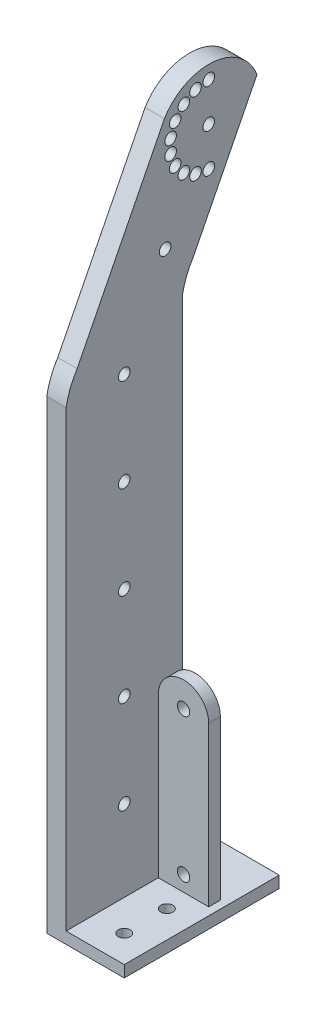
SolidWorks part; units mm, degrees
ref_plane "前视基准面" through (0, 0, 0) normal (0, 0, 1) x (1, 0, 0)
ref_plane "上视基准面" through (0, 0, 0) normal (0, 1, 0) x (1, 0, 0)
ref_plane "右视基准面" through (0, 0, 0) normal (1, 0, 0) x (0, 0, -1)
sketch "草图1" plane through (0, 0, 0) normal (1, 0, 0) x (0, 0, -1)
  line L0 (-15, 0) -> (15, 0)
  line L1 (-15, 0) -> (-15, 120)
  line L2 (15, 0) -> (15, 130)
  line L3 (17.8333, 137.2485) -> (34.2776, 169.8061)
  line L4 (-12.1667, 127.2485) -> (10.3753, 171.8787)
  line L5 (13.1525, 169.9179) -> (21.8127, 164.9179) construction
  line L7 (11.218, 143.9417) -> (10.5417, 142.6028) construction
  line L8 (21.8127, 164.9179) -> (15.3848, 172.5784) construction
  line L9 (21.8127, 164.9179) -> (11.9646, 166.6544) construction
  line L10 (11.9646, 163.1814) -> (21.8127, 164.9179) construction
  line L11 (21.8127, 164.9179) -> (18.3925, 155.521) construction
  line L12 (21.8127, 164.9179) -> (21.8127, 154.9179) construction
  line L13 (18.3925, 174.3148) -> (21.8127, 164.9179) construction
  line L14 (21.8127, 164.9179) -> (13.1525, 159.9179) construction
  line L15 (21.8127, 164.9179) -> (21.8127, 174.9179) construction
  line L16 (15.3848, 157.2575) -> (21.8127, 164.9179) construction
  arc A0 (15, 130) -> (17.8333, 137.2485) centre (34.6882, 126.4823) cw
  arc A1 (-12.1667, 127.2485) -> (-15, 120) centre (4.6882, 116.4823) ccw
  circle A2 centre (0, 23.9341) radius 1.5
  circle A3 centre (0, 47.9341) radius 1.5
  circle A4 centre (0, 71.9341) radius 1.5
  circle A5 centre (0, 95.9341) radius 1.5
  circle A7 centre (21.8127, 164.9179) radius 10 construction
  circle A8 centre (10.5417, 142.6028) radius 1.5
  circle A9 centre (0, 119.9341) radius 1.5
  arc A10 (34.2776, 169.8061) -> (10.3753, 171.8787) centre (21.8127, 164.9179) ccw
  circle A11 centre (21.8127, 164.9179) radius 1.5
  circle A13 centre (11.9646, 166.6544) radius 1.5
  circle A14 centre (11.9646, 163.1814) radius 1.5
  circle A15 centre (13.1525, 159.9179) radius 1.5
  circle A16 centre (15.3848, 157.2575) radius 1.5
  circle A19 centre (21.8127, 154.9179) radius 1.5
  circle A20 centre (18.3925, 155.521) radius 1.5
  circle A21 centre (13.1525, 169.9179) radius 1.5
  circle A22 centre (15.3848, 172.5784) radius 1.5
  circle A23 centre (18.3925, 174.3148) radius 1.5
  circle A24 centre (21.8127, 174.9179) radius 1.5
  point P3 (0, 0)
  dimension "D5" = 20
  dimension "D7" = 20
  dimension "D4" = 3
  dimension "D9" = 3
  dimension "D11" = 3
  dimension "D16" = 20
  dimension "D20" = 20
  dimension "D22" = 20
  dimension "D24" = 20
  dimension "D1" = 30
  dimension "D2" = 120
  dimension "D3" = 130
  dimension "D6" = 24
  dimension "D8" = 25
  dimension "D12" = 25
  dimension "D10" = 15
  dimension "D13" = 24
  dimension "D14" = 24
  dimension "D15" = 24
  dimension "D17" = 20
  dimension "D18" = 20
  dimension "D19" = 20
  dimension "D21" = 20
  dimension "D23" = 20
extrude "凸台-拉伸2" add sketch "草图1" against normal blind 5
ref_plane "基准面1" through (-5, 0, 0) normal (-1, 0, 0) x (0, 0, 1)
sketch "草图3" plane through (-5, 0, 0) normal (-1, 0, 0) x (0, 0, 1)
  line L25 (-10, 5) -> (10, 5)
  line L26 (-10, 130.4183) -> (-10, 5)
  line L27 (10, 5) -> (10, 119.5247)
  line L28 (-28.6572, 169.7687) -> (-13.4775, 139.7151)
  line L29 (7.8255, 124.7531) -> (-14.7389, 169.4276)
  line L30 (-10, 5) -> (10, 5)
  line L31 (-10, 130.4183) -> (-10, 5)
  line L32 (10, 5) -> (10, 119.5247)
  line L33 (-28.6572, 169.7687) -> (-13.4775, 139.7151)
  line L34 (7.8255, 124.7531) -> (-14.7389, 169.4276)
  arc A19 (10, 119.5247) -> (7.8255, 124.7531) centre (-4.6882, 116.4823) ccw
  arc A20 (-10, 130.4183) -> (-13.4775, 139.7151) centre (-34.6882, 126.4823) ccw
  arc A21 (-14.7389, 169.4276) -> (-28.6572, 169.7687) centre (-21.8127, 164.9179) ccw
  arc A22 (10, 119.5247) -> (7.8255, 124.7531) centre (-4.6882, 116.4823) ccw
  arc A23 (-10, 130.4183) -> (-13.4775, 139.7151) centre (-34.6882, 126.4823) ccw
  arc A24 (-14.7389, 169.4276) -> (-28.6572, 169.7687) centre (-21.8127, 164.9179) ccw
  dimension "D1" = 5
extrude "切除-拉伸2" cut sketch "草图3" against normal blind 1
ref_plane "基准面3" through (-30, 0, 0) normal (-1, 0, 0) x (0, 0, 1)
ref_plane "基准面4" through (0, 0, 0) normal (0, -1, 0) x (-1, 0, 0)
sketch "草图4" plane through (0, 0, 0) normal (0, -1, 0) x (-1, 0, 0)
  line L0 (5, -15) -> (-15, -15)
  line L1 (5, -15) -> (0, -15) construction
  line L2 (-15, -15) -> (-15, 25)
  line L3 (-15, 25) -> (8, 25)
  line L4 (5, 15) -> (5, -15)
  line L5 (5, -15) -> (5, 15) construction
  line L9 (8, 25) -> (8, 15)
  line L10 (8, 15) -> (5, 15)
  point P6 (8.7009, 15)
  point P7 (6.7364, 15)
  dimension "D2" = 40
  dimension "D3" = 3
  dimension "D4" = 10
  dimension "D5" = 20
extrude "凸台-拉伸3" add sketch "草图4" against normal blind 3
sketch "草图5" plane through (0, 0, 0) normal (0, -1, 0) x (1, 0, 0)
  line L0 (-8, -15) -> (-8, -25) construction
  line L1 (-5, -15) -> (-8, -15) construction
  line L3 (-5, 15) -> (15, 15) construction
  circle A1 centre (8, 8) radius 1.55
  circle A2 centre (-3, -20) radius 1.55
  circle A3 centre (8, -3) radius 1.55
  dimension "D1" = 5
  dimension "D4" = 3.1
  dimension "D3" = 3.1
  dimension "D6" = 11
  dimension "D7" = 3.1
  dimension "D2" = 5
  dimension "D5" = 7
extrude "切除-拉伸3" cut sketch "草图5" against normal blind 10
sketch "草图6" plane through (0, 0, 0) normal (1, 0, 0) x (0, 0, -1)
  line L0 (15, 3) -> (-15, 3) construction
  line L1 (8.8, 3) -> (11.8, 3)
  line L2 (8.8, 3) -> (8.8, 44)
  line L3 (8.8, 44) -> (11.8, 44)
  line L4 (11.8, 3) -> (11.8, 44)
  line L5 (15, 3) -> (15, 130) construction
  dimension "D1" = 3
  dimension "D2" = 3.2
  dimension "D3" = 41
extrude "凸台-拉伸4" add sketch "草图6" along normal blind 13
sketch "草图8" plane through (0, 0, -11.8) normal (0, 0, -1) x (-1, 0, 0)
  line L0 (-13, 44) -> (0, 44) construction
  line L1 (-13, 44) -> (0, 44)
  arc A0 (0, 44) -> (-13, 44) centre (-6.5, 44) ccw
extrude "凸台-拉伸5" add sketch "草图8" against normal blind 3
sketch "草图9" plane through (0, 0, -11.8) normal (0, 0, -1) x (-1, 0, 0)
  circle A0 centre (-6.5, 44) radius 1.6
  circle A1 centre (-6.5, 7) radius 1.6
  dimension "D1" = 37
extrude "切除-拉伸4" cut sketch "草图9" against normal blind 3
